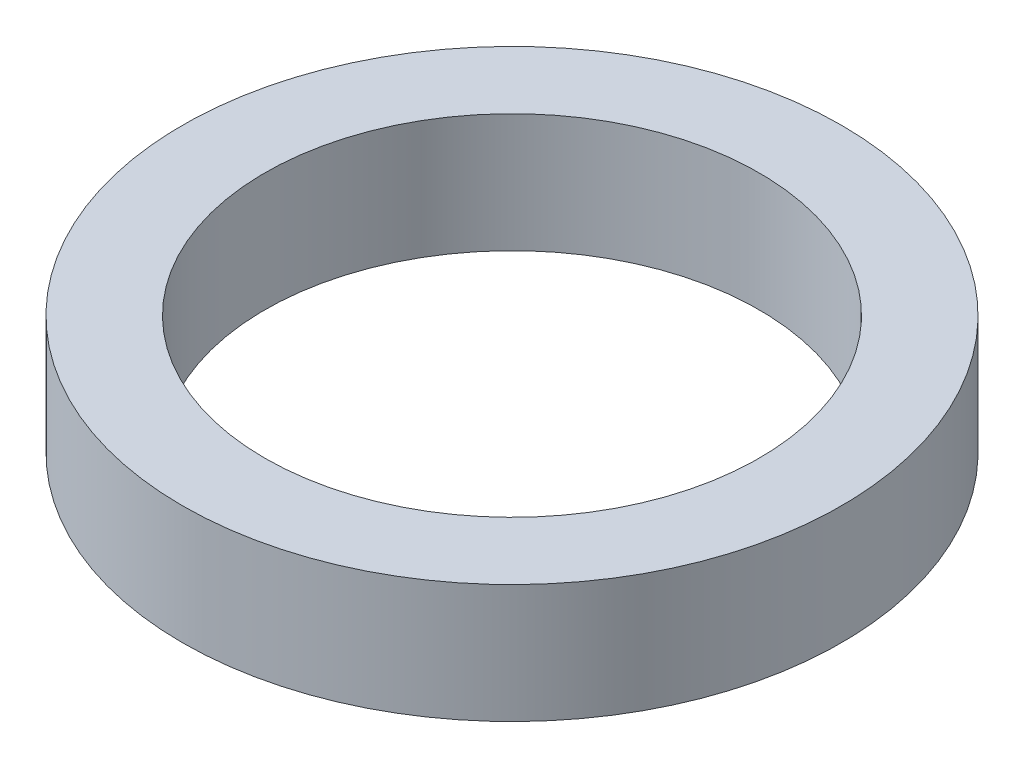
SolidWorks part; units mm, degrees
ref_plane "Front Plane" through (0, 0, 0) normal (0, 0, 1) x (1, 0, 0)
ref_plane "Top Plane" through (0, 0, 0) normal (0, 1, 0) x (1, 0, 0)
ref_plane "Right Plane" through (0, 0, 0) normal (1, 0, 0) x (0, 0, -1)
sketch "Sketch1" plane through (0, 0, 0) normal (0, 1, 0) x (1, 0, 0)
  circle A0 centre (0, 0) radius 50
  dimension "FLANGE_OD" = 100
extrude "Boss-Extrude1" add sketch "Sketch1" along normal blind 18
sketch "Sketch2" plane through (0, 0, 0) normal (0, 1, 0) x (1, 0, 0)
  circle A0 centre (0, 0) radius 37.5
  dimension "BORE_D" = 75
extrude "Cut-Extrude1" cut sketch "Sketch2" along normal through all
sketch "Sketch3" plane through (0, 18, 0) normal (0, 1, 0) x (1, 0, 0)
  circle A0 centre (0, 0) radius 21.8604 construction
  circle A1 centre (-21.8604, 0) radius 1.8743
  dimension "BOLT_D" = 3.7486
  dimension "BOLT_PCD" = 43.7209
extrude "Cut-Extrude2" cut sketch "Sketch3" against normal blind 16.6224 rebuild error yes
pattern_circular "CirPattern1" count 4 over 360 rebuild error yes
